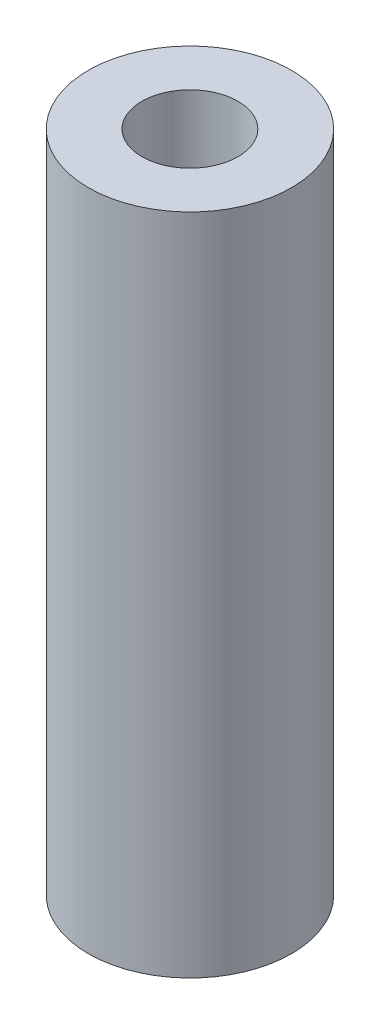
SolidWorks part; units mm, degrees
ref_plane "Front Plane" through (0, 0, 0) normal (0, 0, 1) x (1, 0, 0)
ref_plane "Top Plane" through (0, 0, 0) normal (0, 1, 0) x (1, 0, 0)
ref_plane "Right Plane" through (0, 0, 0) normal (1, 0, 0) x (0, 0, -1)
sketch "Sketch1" plane through (0, 0, 0) normal (0, 1, 0) x (1, 0, 0)
  circle A0 centre (0, 0) radius 5.975
  dimension "D1" = 11.95
extrude "Boss-Extrude1" add sketch "Sketch1" along normal blind 39
sketch "Sketch2" plane through (0, 39, 0) normal (0, 1, 0) x (1, 0, 0)
  circle A0 centre (0, 0) radius 2.825
  dimension "D1" = 5.65
extrude "Cut-Extrude1" cut sketch "Sketch2" against normal blind 4.5
sketch "Sketch3" plane through (0, 0, 0) normal (0, -1, 0) x (1, 0, 0)
  circle A0 centre (0, 0) radius 9.645
extrude "Cut-Extrude2" [suppressed] cut sketch "Sketch3" against normal blind 25
sketch "Sketch4" plane through (0, 39, 0) normal (0, 1, 0) x (1, 0, 0)
  circle A0 centre (0, 0) radius 5.955
  circle A1 centre (0, 0) radius 3.5804
extrude "Cut-Extrude3" [suppressed] cut sketch "Sketch4" against normal blind 30
